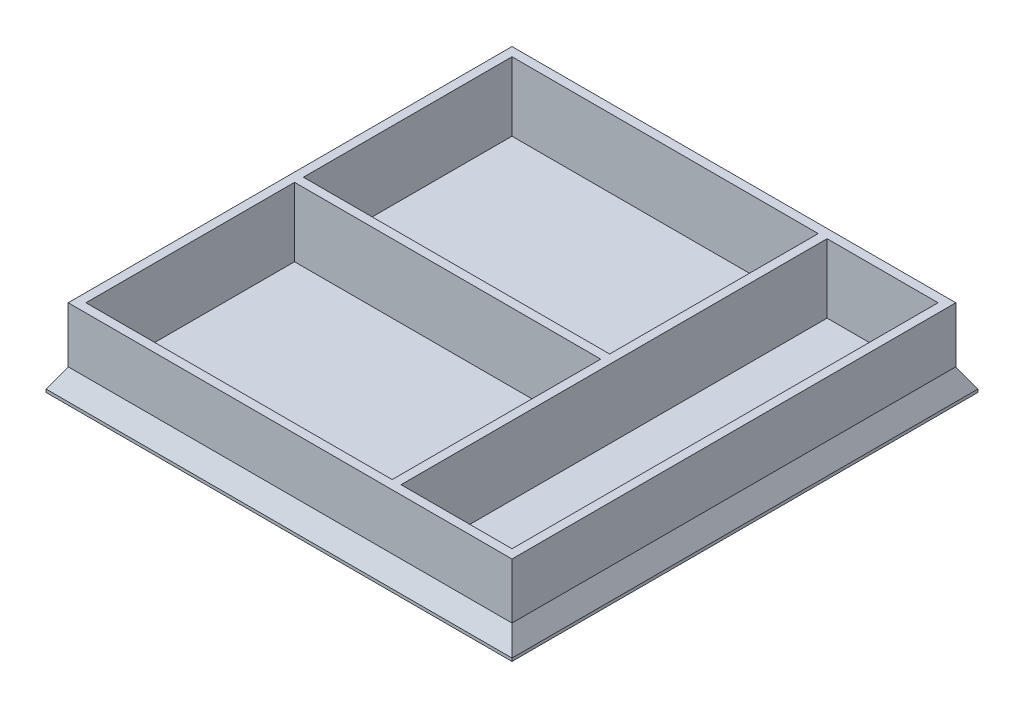
SolidWorks part; units mm, degrees
ref_plane "Přední rovina" through (0, 0, 0) normal (0, 0, 1) x (1, 0, 0)
ref_plane "Horní rovina" through (0, 0, 0) normal (0, 1, 0) x (1, 0, 0)
ref_plane "Pravá rovina" through (0, 0, 0) normal (1, 0, 0) x (0, 0, -1)
sketch "Skica1" plane through (0, 0, 0) normal (0, 1, 0) x (1, 0, 0)
  line L0 (-84, 84) -> (0, 0) construction
  line L1 (0, 0) -> (-84, 0)
  line L2 (0, 0) -> (0, 84)
  line L3 (0, 84) -> (-84, 84)
  line L4 (-84, 0) -> (-84, 84)
  line L5 (-84, 0) -> (0, 84) construction
  line L7 (-82, 82) -> (-2, 82)
  line L8 (-82, 82) -> (-82, 2)
  line L9 (-82, 2) -> (-2, 2)
  line L10 (-2, 82) -> (-2, 2)
  line L11 (-82, 82) -> (-2, 2) construction
  line L12 (-82, 2) -> (-2, 82) construction
  line L13 (-82, 42) -> (-2, 42) construction
  line L15 (-23.6, 80.4) -> (-3.6, 80.4)
  line L16 (-23.6, 80.4) -> (-23.6, 3.6)
  line L17 (-23.6, 3.6) -> (-3.6, 3.6)
  line L18 (-3.6, 80.4) -> (-3.6, 3.6)
  line L19 (-80.4, 80.4) -> (-25.2, 80.4)
  line L20 (-80.4, 80.4) -> (-80.4, 42.8)
  line L21 (-80.4, 42.8) -> (-25.2, 42.8)
  line L22 (-25.2, 80.4) -> (-25.2, 42.8)
  line L23 (-80.4, 41.2) -> (-25.2, 41.2)
  line L24 (-80.4, 41.2) -> (-80.4, 3.6)
  line L25 (-80.4, 3.6) -> (-25.2, 3.6)
  line L26 (-25.2, 41.2) -> (-25.2, 3.6)
  point P4 (-42, 42)
  dimension "D1" = 84
  dimension "D2" = 84
  dimension "D3" = 80
  dimension "D4" = 80
  dimension "D5" = 1.6
  dimension "D6" = 1.6
  dimension "D7" = 1.6
  dimension "D8" = 1.6
  dimension "D9" = 1.6
  dimension "D10" = 1.6
  dimension "D11" = 0.8
  dimension "D12" = 0.8
  dimension "D13" = 1.6
  dimension "D14" = 20
  dimension "D15" = 1.6
  dimension "D16" = 1.6
extrude "Přidat vysunutím1" add sketch "Skica1" along normal blind 1.6 contours L3 L4 L1 L2
extrude "Přidat vysunutím2" add sketch "Skica1<3>" along normal blind 14 contours L10 L7 L8 L9 L15 L18 L17 L16 L19 L22 L21 L20 L23 L26 L25 L24 region at (-40.3045, 0, -42)
sketch "Skica1<3>" plane through (0, 0, 0) normal (0, 1, 0) x (1, 0, 0) same geometry as "Skica1"
extrude "Přidat vysunutím3" add sketch "Skica1<4>" along normal blind 4 contours L4 L1 L2 L3 L7 L10 L9 L8 region at (-42, 0, -1.1879)
sketch "Skica1<4>" plane through (0, 0, 0) normal (0, 1, 0) x (1, 0, 0) same geometry as "Skica1"
chamfer "Zkosení2" distance 2 angle 60 4 edges at (-84, 4, -42) (-42, 4, -84) (0, 4, -42) (-42, 4, 0) first distance on face at (-42, 4, -42)
